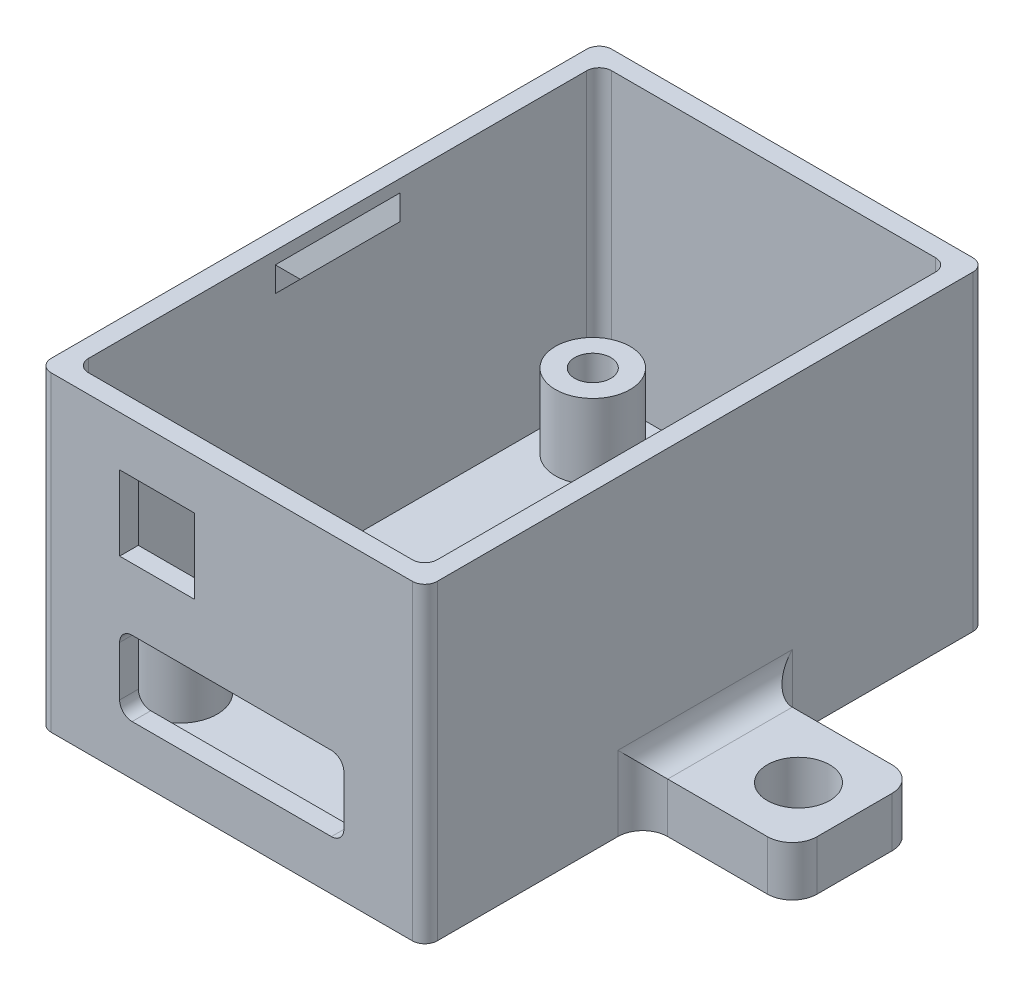
SolidWorks part; units mm, degrees
ref_plane "Front Plane" through (0, 0, 0) normal (0, 0, 1) x (1, 0, 0)
ref_plane "Top Plane" through (0, 0, 0) normal (0, 1, 0) x (1, 0, 0)
ref_plane "Right Plane" through (0, 0, 0) normal (1, 0, 0) x (0, 0, -1)
sketch "Sketch1" plane through (0, 0, 0) normal (0, 1, 0) x (1, 0, 0)
  line L1 (-15.5, 22.5) -> (15.5, 22.5)
  line L2 (-15.5, 22.5) -> (-15.5, -22.5)
  line L3 (-15.5, -22.5) -> (15.5, -22.5)
  line L4 (15.5, 22.5) -> (15.5, -22.5)
  line L5 (-15.5, 22.5) -> (15.5, -22.5) construction
  line L6 (-15.5, -22.5) -> (15.5, 22.5) construction
  point P0 (0, 0)
  dimension "D1" = 45
  dimension "D2" = 31
extrude "Boss-Extrude1" add sketch "Sketch1" along normal blind 25
sketch "Sketch2" plane through (0, 25, 0) normal (0, 1, 0) x (1, 0, 0)
  line L1 (-14, 21) -> (14, 21)
  line L2 (-14, 21) -> (-14, -21)
  line L3 (-14, -21) -> (14, -21)
  line L4 (14, 21) -> (14, -21)
  line L5 (-14, 21) -> (14, -21) construction
  line L6 (-14, -21) -> (14, 21) construction
  point P0 (0, 0)
  dimension "D1" = 42
  dimension "D2" = 28
extrude "Cut-Extrude1" cut sketch "Sketch2" against normal blind 23
sketch "Sketch3" plane through (0, 2, 0) normal (0, 1, 0) x (1, 0, 0)
  line L1 (-10.09, 16.575) -> (10.23, 16.575) construction
  line L2 (-10.09, 16.575) -> (-10.09, -16.575) construction
  line L3 (-10.09, -16.575) -> (10.23, -16.575) construction
  line L4 (10.23, 16.575) -> (10.23, -16.575) construction
  circle A0 centre (-10.09, 16.575) radius 3
  circle A1 centre (10.23, 16.575) radius 3
  circle A2 centre (10.23, -16.575) radius 3
  circle A3 centre (-10.09, -16.575) radius 3
  point P0 (0, 0)
  dimension "D1" = 33.15
  dimension "D2" = 20.32
extrude "Boss-Extrude5" add sketch "Sketch3" along normal blind 6
sketch "Sketch4" plane through (0, 0, 22.5) normal (0, 0, 1) x (1, 0, 0)
  line L0 (-9, 4) -> (9, 4)
  line L1 (-9, 10) -> (-9, 15) construction
  line L2 (-9, 4) -> (-9, 10)
  line L3 (-9, 10) -> (9, 10)
  line L4 (9, 10) -> (9, 4)
  line L6 (-9, 15) -> (-3, 15)
  line L7 (-9, 15) -> (-9, 21)
  line L8 (-9, 21) -> (-3, 21)
  line L9 (-3, 15) -> (-3, 21)
  dimension "D1" = 6
  dimension "D2" = 18
  dimension "D3" = 5
  dimension "D4" = 6
  dimension "D5" = 6
extrude "Cut-Extrude2" cut sketch "Sketch4" against normal blind 1.5
hole_wizard "CSK for M2.5 Flat Head Machine Screw1" positions "Sketch6" profile "Sketch7" countersink size "M2.5" standard "ANSI Metric" end condition through all
sketch "Sketch6" plane through (0, 0, 0) normal (0, -1, 0) x (-1, 0, 0)
  point P0 (-10.23, -16.575)
  point P3 (10.09, -16.575)
  point P6 (10.09, 16.575)
  point P9 (-10.23, 16.575)
sketch "Sketch7" plane through (10.23, 0, 16.575) normal (1, 0, 0) x (0, 0, -1)
  line L0 (0, 0) -> (0, 25)
  line L1 (0, 25) -> (1.45, 25)
  line L2 (1.45, 25) -> (1.45, 1.3)
  line L3 (1.45, 1.3) -> (2.75, 0)
  line L5 (2.75, 0) -> (0, 0)
  line L6 (-1.45, 1.3) -> (-2.75, 0) construction
  line L11 (0, -6.35) -> (0, 107.95) construction
  dimension "Thru Hole Dia." = 2.9
  dimension "Thru Hole Depth" = 25
  dimension "Near C'Sink Dia." = 5.5
  dimension "Near C'Sink Angle" = 90
fillet "Fillet2" radius 1 12 edges at (9, 10, 21.75) (9, 4, 21.75) (-9, 4, 21.75) (-9, 10, 21.75) (15.5, 12.5, 22.5) (14, 13.5, 21) (-15.5, 12.5, 22.5) (-14, 13.5, 21) (-15.5, 12.5, -22.5) (-14, 13.5, -21) (14, 13.5, -21) (15.5, 12.5, -22.5)
sketch "Sketch8" plane through (0, 0, 0) normal (0, 1, 0) x (1, 0, 0)
  line L0 (15.5, 5) -> (27.5, 5)
  line L5 (-27.5, 5) -> (-15.5, 5)
  line L6 (-27.5, 5) -> (-27.5, -5)
  line L7 (15.5, 5) -> (15.5, -5)
  line L8 (15.5, -5) -> (27.5, -5)
  line L9 (27.5, 5) -> (27.5, -5)
  line L10 (15.5, 5) -> (27.5, -5) construction
  line L11 (15.5, -5) -> (27.5, 5) construction
  line L12 (-27.5, -5) -> (-15.5, -5)
  line L13 (-15.5, 5) -> (-15.5, -5)
  line L14 (-27.5, 5) -> (-15.5, -5) construction
  line L15 (-27.5, -5) -> (-15.5, 5) construction
  point P1 (-21.5, 0)
  point P5 (21.5, 0)
  dimension "D1" = 12
  dimension "D2" = 10
extrude "Boss-Extrude6" add sketch "Sketch8" along normal blind 4
sketch "Sketch9" plane through (0, 4, 0) normal (0, 1, 0) x (1, 0, 0)
  circle A0 centre (23, 0) radius 2.5
  circle A1 centre (-23.5, 0) radius 2.5
extrude "Cut-Extrude3" cut sketch "Sketch9" against normal blind 4
fillet "Fillet3" radius 2 4 edges at (-15.5, 2, 5) (-15.5, 2, -5) (15.5, 2, -5) (15.5, 2, 5)
fillet "Fillet4" radius 2 2 edges at (15.5, 4, 0) (-15.5, 4, 0)
sketch "Sketch10" plane through (-14, 0, 0) normal (1, 0, 0) x (0, 0, -1)
  line L1 (-5, 24) -> (5, 24)
  line L2 (-5, 24) -> (-5, 22)
  line L3 (-5, 22) -> (5, 22)
  line L4 (5, 24) -> (5, 22)
  line L5 (-5, 24) -> (5, 22) construction
  line L6 (-5, 22) -> (5, 24) construction
  point P0 (0, 23)
  point P5 (0.3913, 23.7362)
  point P6 (0, 0)
  point P7 (0, 0)
  point P8 (0, 0)
  dimension "D1" = 2
  dimension "D2" = 10
extrude "Boss-Extrude7" add sketch "Sketch10" along normal blind 1
chamfer "Chamfer1" distance 1 angle 45 4 edges at (-13, 23, 5) (-13, 22, 0) (-13, 23, -5) (-13, 24, 0)
sketch "Sketch11" plane through (14, 0, 0) normal (-1, 0, 0) x (0, 0, 1)
  line L1 (-5, 24) -> (5, 24)
  line L2 (-5, 24) -> (-5, 22)
  line L3 (-5, 22) -> (5, 22)
  line L4 (5, 24) -> (5, 22)
  line L5 (-5, 24) -> (5, 22) construction
  line L6 (-5, 22) -> (5, 24) construction
  point P0 (0, 23)
  point P5 (0, 0)
  point P6 (0, 0)
  dimension "D1" = 2
  dimension "D2" = 10
extrude "Boss-Extrude8" add sketch "Sketch11" along normal blind 1
chamfer "Chamfer2" distance 1 angle 45 4 edges at (13, 23, 5) (13, 24, 0) (13, 22, 0) (13, 23, -5)
fillet "Fillet5" radius 2 4 edges at (-27.5, 2, -5) (-27.5, 2, 5) (27.5, 2, -5) (27.5, 2, 5)
